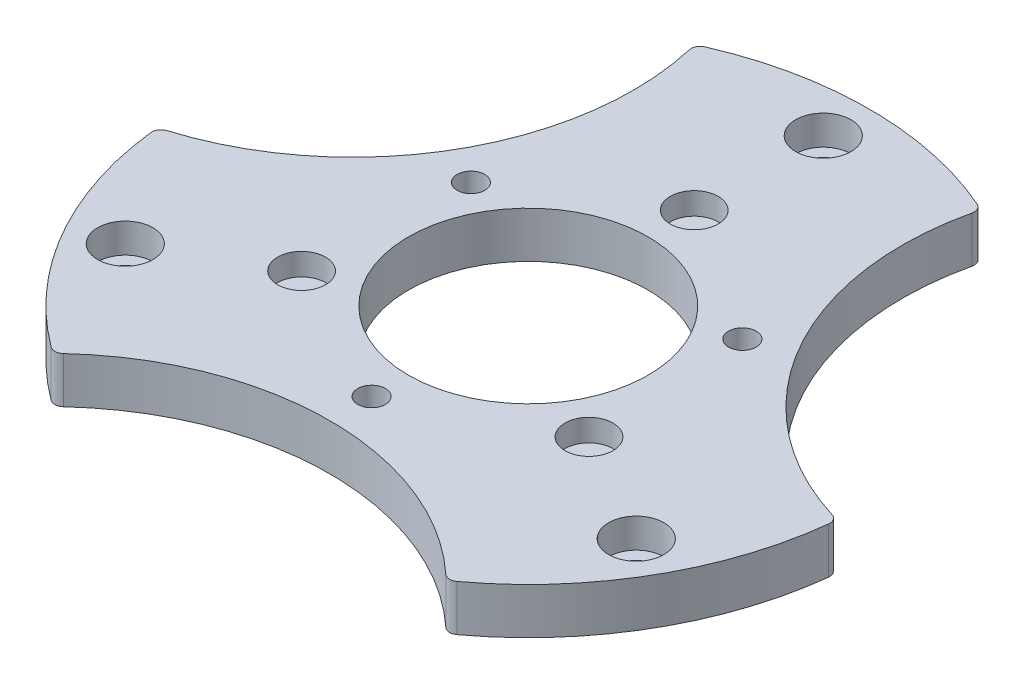
SolidWorks part; units mm, degrees
ref_plane "Front Plane" through (0, 0, 0) normal (0, 0, 1) x (1, 0, 0)
ref_plane "Top Plane" through (0, 0, 0) normal (0, 1, 0) x (1, 0, 0)
ref_plane "Right Plane" through (0, 0, 0) normal (1, 0, 0) x (0, 0, -1)
sketch "Sketch1" plane through (0, 0, 0) normal (0, 1, 0) x (1, 0, 0)
  circle A0 centre (0, 0) radius 37
  circle A1 centre (0, 0) radius 13
  dimension "D1" = 74
  dimension "D2" = 26
extrude "Boss-Extrude1" add sketch "Sketch1" along normal blind 5
sketch "Sketch2" plane through (0, 5, 0) normal (0, 1, 0) x (1, 0, 0)
  circle A0 centre (0, 32) radius 1.65
  dimension "D1" = 3.3
  dimension "D2" = 32
extrude "Cut-Extrude1" cut sketch "Sketch2" against normal through all
pattern_circular "CirPattern1" count 3 over 360 about axis through (0, 5, 0) along (0, -1, 0) of "Cut-Extrude1" reverse direction yes
sketch "Sketch3" plane through (0, 5, 0) normal (0, 1, 0) x (1, 0, 0)
  line L0 (0, 0) -> (45.0333, 26) construction
  line L1 (-1000, 0) -> (49000, 0) construction
  circle A0 centre (45.0333, 26) radius 30.47
  dimension "D2" = 60.94
  dimension "D1" = 30
  dimension "D3" = 52
extrude "Cut-Extrude2" cut sketch "Sketch3" against normal blind 10
pattern_circular "CirPattern2" count 3 over 360 about axis through (0, 5, 0) along (0, -1, 0) of "Cut-Extrude2"
fillet "Fillet1" radius 1 6 edges at (21.3252, 2.5, 30.2363) (-21.3252, 2.5, 30.2363) (-36.848, 2.5, 3.35) (-15.5228, 2.5, -33.5863) (36.848, 2.5, 3.35) (15.5228, 2.5, -33.5863)
sketch "Sketch4" plane through (0, 5, 0) normal (0, 1, 0) x (1, 0, 0)
  circle A0 centre (0, 0) radius 6 construction
  circle A1 centre (0, 18) radius 12 construction
  circle A2 centre (0, 18) radius 0.75
  dimension "D1" = 12
  dimension "D2" = 24
  dimension "D3" = 1.5
extrude "Cut-Extrude3" cut sketch "Sketch4" against normal blind 10
sketch "Sketch6" plane through (0, 5, 0) normal (0, 1, 0) x (1, 0, 0)
  circle A0 centre (0, 18) radius 2.6
  dimension "D1" = 5.2
extrude "Cut-Extrude4" cut sketch "Sketch6" against normal blind 2.4
sketch "Sketch7" plane through (0, 5, 0) normal (0, 1, 0) x (1, 0, 0)
  circle A0 centre (0, 32) radius 3
  dimension "D1" = 6
extrude "Cut-Extrude5" cut sketch "Sketch7" against normal blind 3.2
pattern_circular "CirPattern3" count 3 over 360 about axis through (0, 5, 0) along (0, -1, 0) of "Cut-Extrude3", "Cut-Extrude4", "Cut-Extrude5" reverse direction yes
sketch "Sketch8" plane through (0, 5, 0) normal (0, 1, 0) x (1, 0, 0)
  line L0 (14.7224, 8.5) -> (0, 0) construction
  line L1 (-1000, 0) -> (49000, 0) construction
  circle A0 centre (14.7224, 8.5) radius 1.5
  dimension "D3" = 3
  dimension "D1" = 30
  dimension "D2" = 17
extrude "Cut-Extrude6" cut sketch "Sketch8" against normal blind 10
pattern_circular "CirPattern4" count 3 over 360 about axis through (0, 5, 0) along (0, -1, 0) of "Cut-Extrude6" reverse direction yes
